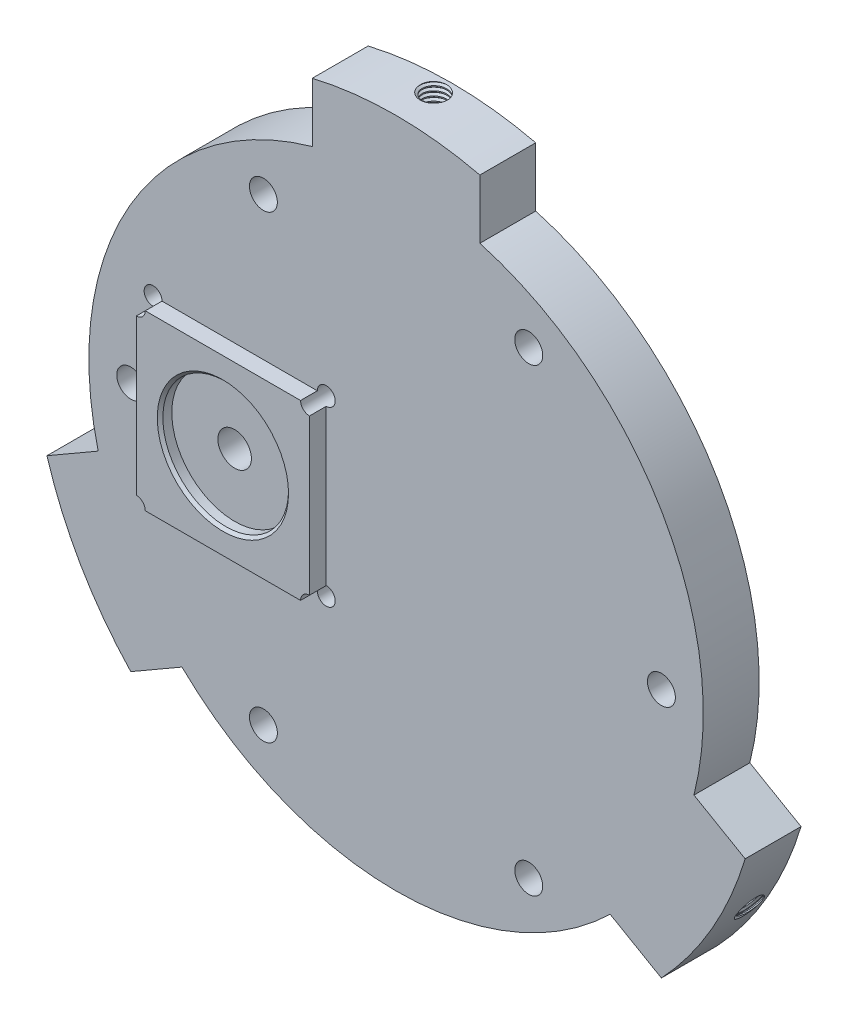
SolidWorks part; units mm, degrees
ref_plane "Ebene vorne" through (0, 0, 0) normal (0, 0, 1) x (1, 0, 0)
ref_plane "Ebene oben" through (0, 0, 0) normal (0, 1, 0) x (1, 0, 0)
ref_plane "Ebene rechts" through (0, 0, 0) normal (1, 0, 0) x (0, 0, -1)
sketch "Skizze1" plane through (0, 0, 0) normal (0, 0, 1) x (1, 0, 0)
  circle A0 centre (0, 0) radius 55
  dimension "D1" = 110
extrude "Aufsatz-Linear austragen1" add sketch "Skizze1" along normal blind 10
sketch "Skizze2" plane through (0, 0, 10) normal (0, 0, 1) x (1, 0, 0)
  circle A0 centre (-28, 0) radius 3
  dimension "D1" = 28
extrude "Schnitt-Linear austragen1" cut sketch "Skizze2" against normal blind 10 contours A0
sketch "Skizze3" plane through (0, 0, 10) normal (0, 0, 1) x (1, 0, 0)
  circle A0 centre (-47.5, 0) radius 2.5
  dimension "D1" = 5
  dimension "D2" = 47.5
extrude "Schnitt-Linear austragen2" cut sketch "Skizze3" against normal blind 10
pattern_circular "Kreismuster1" count 6 over 360 about axis through (0, 0, 0) along (0, 0, 1) of "Schnitt-Linear austragen2"
sketch "Skizze4" plane through (0, 0, 10) normal (0, 0, 1) x (1, 0, 0)
  line L1 (-43.5, 15.5) -> (-12.5, 15.5)
  line L2 (-43.5, 15.5) -> (-43.5, -15.5)
  line L3 (-43.5, -15.5) -> (-12.5, -15.5)
  line L4 (-12.5, 15.5) -> (-12.5, -15.5)
  line L5 (-43.5, 15.5) -> (-12.5, -15.5) construction
  line L6 (-43.5, -15.5) -> (-12.5, 15.5) construction
  point P0 (-28, 0)
  dimension "D1" = 31
  dimension "D2" = 31
extrude "Aufsatz-Linear austragen2" add sketch "Skizze4" along normal blind 3
sketch "Skizze5" plane through (0, 0, 13) normal (0, 0, 1) x (1, 0, 0)
  circle A0 centre (-43.5, 15.5) radius 1.6
  circle A1 centre (-12.5, 15.5) radius 1.6
  circle A2 centre (-12.5, -15.5) radius 1.6
  circle A3 centre (-43.5, -15.5) radius 1.6
  dimension "D1" = 3.2
extrude "Schnitt-Linear austragen3" cut sketch "Skizze5" against normal blind 30
sketch "Skizze6" plane through (0, 0, 0) normal (0, 0, -1) x (-1, 0, 0)
  circle A0 centre (12.5, 15.5) radius 2.8
  circle A1 centre (12.5, -15.5) radius 2.8
  circle A2 centre (43.5, -15.5) radius 2.8
  circle A3 centre (43.5, 15.5) radius 2.8
  dimension "D1" = 5.6
extrude "Schnitt-Linear austragen4" cut sketch "Skizze6" against normal blind 2.2
sketch "Skizze7" plane through (0, 0, 13) normal (0, 0, 1) x (1, 0, 0)
  circle A0 centre (-28, 0) radius 3
extrude "Schnitt-Linear austragen5" cut sketch "Skizze7" against normal blind 5
sketch "Skizze8" plane through (0, 0, 13) normal (0, 0, 1) x (1, 0, 0)
  circle A0 centre (-28, 0) radius 11.25
  dimension "D1" = 22.5
extrude "Schnitt-Linear austragen6" cut sketch "Skizze8" against normal blind 2.1
chamfer "Fase1" distance 0.5 angle 45 1 edges at (-16.75, 0, 13)
sketch "Skizze9" plane through (0, 0, 10) normal (0, 0, 1) x (1, 0, 0)
  line L2 (-15, 63.5025) -> (-15, 52.915)
  line L3 (-15, 52.915) -> (15, 52.915)
  line L4 (15, 63.5025) -> (15, 52.915)
  arc A0 (15, 63.5025) -> (-15, 63.5025) centre (0, 0) ccw
  circle A1 centre (0, 0) radius 55 construction
  point P3 (0, 65.25)
  dimension "D1" = 130.5
  dimension "D2" = 30
  dimension "D3" = 15
extrude "Aufsatz-Linear austragen3" add sketch "Skizze9" against normal blind 10
pattern_circular "Kreismuster2" count 3 over 360 about axis through (0, 0, 0) along (0, 0, 1) of "Aufsatz-Linear austragen3"
ref_plane "Ebene1" through (0, 70.5, 0) normal (0, 1, 0) x (1, 0, 0)
sketch "Skizze10" plane through (0, 70.5, 0) normal (0, 1, 0) x (1, 0, 0)
  line L0 (15, 0) -> (-15, 0) construction
  circle A0 centre (0, -3) radius 2.2
  dimension "D2" = 4.4
  dimension "D1" = 3
extrude "Schnitt-Linear austragen7" cut sketch "Skizze10" against normal blind 17
pattern_circular "Kreismuster3" count 3 over 360 about axis through (0, 0, 0) along (0, 0, 1) of "Schnitt-Linear austragen7"
thread "Gewinde1" pitch 0.8 start angle 0, offset 0, length 17, pitch 0.8, diameter 4.4
ref_plane "Ebene2" through (-2.2, 53.5, 3) normal (0, 0, 1) x (-1, 0, 0)
sketch "Gewindeprofil1" plane through (-2.2, 53.5, 3) normal (0, 0, 1) x (-1, 0, 0)
  line L0 (0, 0) -> (0, 0.8) construction
  line L1 (0, 0) -> (0.433, 0.25)
  line L2 (0.433, 0.25) -> (0.433, 0.35)
  line L3 (0.433, 0.35) -> (0, 0.6)
  line L4 (0.433, 0.3) -> (0, 0.3) construction
  line L11 (0, 0) -> (0, 0.6)
  point P2 (0, 0)
  dimension "Pitch" = 0.8
  dimension "Profile_Angle" = 60
  dimension "Profile_Land" = 0.1
  dimension "Profile_Height" = 0.433
thread "Gewinde2" pitch 0.8 profile "Gewindeprofil2" start angle 0, offset 0, length 17, pitch 0.8, diameter 4.4
ref_plane "Ebene3" through (46.3324, -26.75, 5.2) normal (-0.5, -0.866, 0) x (0, 0, 1)
sketch "Gewindeprofil2" plane through (46.3324, -26.75, 5.2) normal (-0.5, -0.866, 0) x (0, 0, 1)
  line L0 (0, 0) -> (0, 0.8) construction
  line L1 (0, 0) -> (0.433, 0.25)
  line L2 (0.433, 0.25) -> (0.433, 0.35)
  line L3 (0.433, 0.35) -> (0, 0.6)
  line L4 (0.433, 0.3) -> (0, 0.3) construction
  line L11 (0, 0) -> (0, 0.6)
  point P2 (0, 0)
  dimension "Pitch" = 0.8
  dimension "Profile_Angle" = 60
  dimension "Profile_Land" = 0.1
  dimension "Profile_Height" = 0.433
thread "Gewinde3" pitch 0.8 profile "Gewindeprofil3" start angle 0, offset 0, length 17, pitch 0.8, diameter 4.4
ref_plane "Ebene4" through (-46.3324, -26.75, 0.8) normal (0.5, -0.866, 0) x (0, 0, -1)
sketch "Gewindeprofil3" plane through (-46.3324, -26.75, 0.8) normal (0.5, -0.866, 0) x (0, 0, -1)
  line L0 (0, 0) -> (0, 0.8) construction
  line L1 (0, 0) -> (0.433, 0.25)
  line L2 (0.433, 0.25) -> (0.433, 0.35)
  line L3 (0.433, 0.35) -> (0, 0.6)
  line L4 (0.433, 0.3) -> (0, 0.3) construction
  line L11 (0, 0) -> (0, 0.6)
  point P2 (0, 0)
  dimension "Pitch" = 0.8
  dimension "Profile_Angle" = 60
  dimension "Profile_Land" = 0.1
  dimension "Profile_Height" = 0.433
